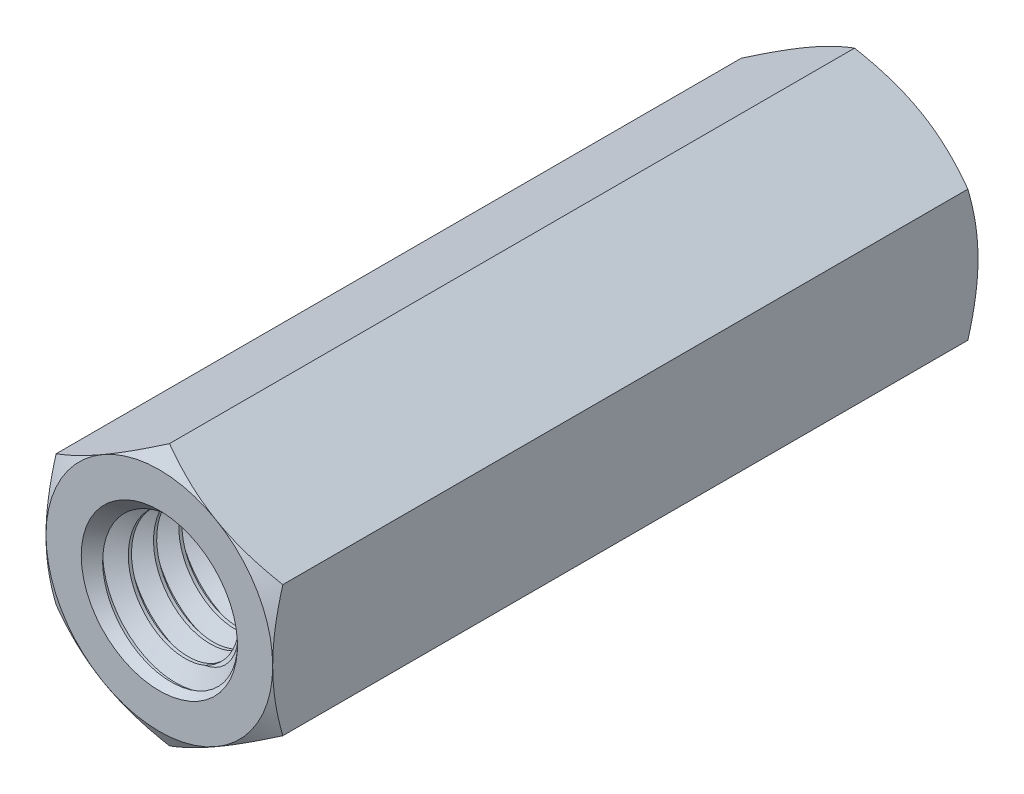
SolidWorks part; units mm, degrees
ref_plane "Front Plane" through (0, 0, 0) normal (0, 0, 1) x (1, 0, 0)
ref_plane "Top Plane" through (0, 0, 0) normal (0, 1, 0) x (1, 0, 0)
ref_plane "Right Plane" through (0, 0, 0) normal (1, 0, 0) x (0, 0, -1)
sketch "Sketch3" plane through (0, 0, 0) normal (1, 0, 0) x (0, 0, -1)
  line L0 (-7, 0) -> (7, 0) construction
  line L1 (0, 2.25) -> (0, -2.25) construction
  line L2 (-7, 1.5) -> (-7, -1.5) construction
  point P2 (0.7, 0)
  point P3 (-0.7, 0)
  dimension "D1" = 6.3
  dimension "Length" = 14
  dimension "Min Thread Length" = 6.3
  dimension "Thread Dia" = 3
  dimension "Hex" = 4.5
sketch "Sketch1" plane through (0, 0, 0) normal (0, 0, 1) x (1, 0, 0)
  line L1 (0, 2.5981) -> (-2.25, 1.299)
  line L2 (-2.25, 1.299) -> (-2.25, -1.299)
  line L3 (-2.25, -1.299) -> (0, -2.5981)
  line L4 (0, -2.5981) -> (2.25, -1.299)
  line L5 (2.25, -1.299) -> (2.25, 1.299)
  line L6 (2.25, 1.299) -> (0, 2.5981)
  circle A0 centre (0, 0) radius 2.25 construction
  circle A1 centre (0, 0) radius 1.5
extrude "Extrude1" add sketch "Sketch1" along normal up to vertex (7 mm away) and the other way up to vertex (7 mm away) up to point (0, 0, 7) other way up to point (0, 0, -7)
sketch "Sketch11" plane through (0, 0, -7) normal (0, 0, -1) x (-1, 0, 0)
  circle A0 centre (0, 0) radius 1.5 construction
  circle A1 centre (0, 0) radius 1.5
curve "Helix/Spiral1" pitch 0.5 height 14.5 radius 1.5 centre (0, 0, -7) axis (0, 0, 1) start towards (0, 1, 0) parameters "Pitch"=0.5
sketch "Sketch12" plane through (0, 0, 0) normal (1, 0, 0) x (0, 0, -1)
  line L0 (7.4375, 1.5) -> (7, 1.5)
  line L1 (7.4375, 1.5) -> (7.25, 1.1752)
  line L2 (7.25, 1.1752) -> (7.1875, 1.1752)
  line L3 (7.1875, 1.1752) -> (7, 1.5)
  line L4 (7.2187, 1.1752) -> (7.2187, 1.5) construction
  line L5 (7.3438, 1.3376) -> (7.0938, 1.3376) construction
  dimension "D1" = 0.0625
  dimension "D2" = 0.25
  dimension "D3" = 60
sweep "Sweep1" add profiles "Sketch12" path "Helix/Spiral1"
sketch "Sketch6" plane through (0, 0, -7) normal (0, 0, -1) x (-1, 0, 0)
  line L6 (0, 2.5981) -> (-2.25, 1.299)
  line L7 (-2.25, 1.299) -> (-2.25, -1.299)
  line L8 (-2.25, -1.299) -> (0, -2.5981)
  line L9 (0, -2.5981) -> (2.25, -1.299)
  line L10 (2.25, -1.299) -> (2.25, 1.299)
  line L11 (2.25, 1.299) -> (0, 2.5981)
  line L12 (0, 2.5981) -> (-2.25, 1.299)
  line L13 (-2.25, 1.299) -> (-2.25, -1.299)
  line L14 (-2.25, -1.299) -> (0, -2.5981)
  line L15 (0, -2.5981) -> (2.25, -1.299)
  line L16 (2.25, -1.299) -> (2.25, 1.299)
  line L17 (2.25, 1.299) -> (0, 2.5981)
  dimension "D1" = 0
extrude "Extrude2" cut sketch "Sketch6" along normal through all
sketch "Sketch7" plane through (0, 0, -7) normal (0, 0, -1) x (-1, 0, 0)
  circle A2 centre (0, 0) radius 1.5508
  circle A3 centre (0, 0) radius 1.5508
  dimension "D1" = 0.0508
extrude "Extrude3" cut sketch "Sketch7" against normal through all draft 43
sketch "Sketch8" plane through (0, 0, -7) normal (0, 0, -1) x (-1, 0, 0)
  circle A0 centre (0, 0) radius 2.25 construction
  circle A1 centre (0, 0) radius 2.25
extrude "Extrude4" cut sketch "Sketch8" against normal through all draft 60 flip side to cut
mirror "Mirror1" about plane through (0, 0, 0) normal (0, 0, 1) of "Extrude2", "Extrude3", "Extrude4"
sketch "Sketch9" plane through (0, 0, 0) normal (1, 0, 0) x (0, 0, -1)
  line L1 (-0.7, 1.5508) -> (0.7, 1.5508)
  line L2 (-0.7, 1.5508) -> (-0.7, 0)
  line L3 (-0.7, 0) -> (0.7, 0)
  line L4 (0.7, 1.5508) -> (0.7, 0)
  line L7 (-7, 0) -> (7, 0) construction
revolve "Revolve" add sketch "Sketch9" angle 360 about L0
sketch "Sketch10" plane through (0, 0, 0) normal (1, 0, 0) x (0, 0, -1)
  line L0 (7, 1.5) -> (0.7, 1.5)
  line L1 (-7, 1.5) -> (-0.7, 1.5)
  line L2 (0.7, 1.5) -> (0.7, -1.5)
  line L3 (-7, -1.5) -> (-0.7, -1.5)
  line L4 (-0.7, 1.5) -> (-0.7, -1.5)
  line L5 (0.7, -1.5) -> (7, -1.5)
equation "\"D1@Sketch3\" = \"Min Thread Length@Sketch3\""
equation "\"D3@Helix/Spiral1\" = \"Length@Sketch3\"+\"Pitch@Helix/Spiral1\""
equation "\"D1@Sketch12\" = \"Pitch@Helix/Spiral1\"*.125"
equation "\"D2@Sketch12\" = \"Pitch@Helix/Spiral1\"*.5"
